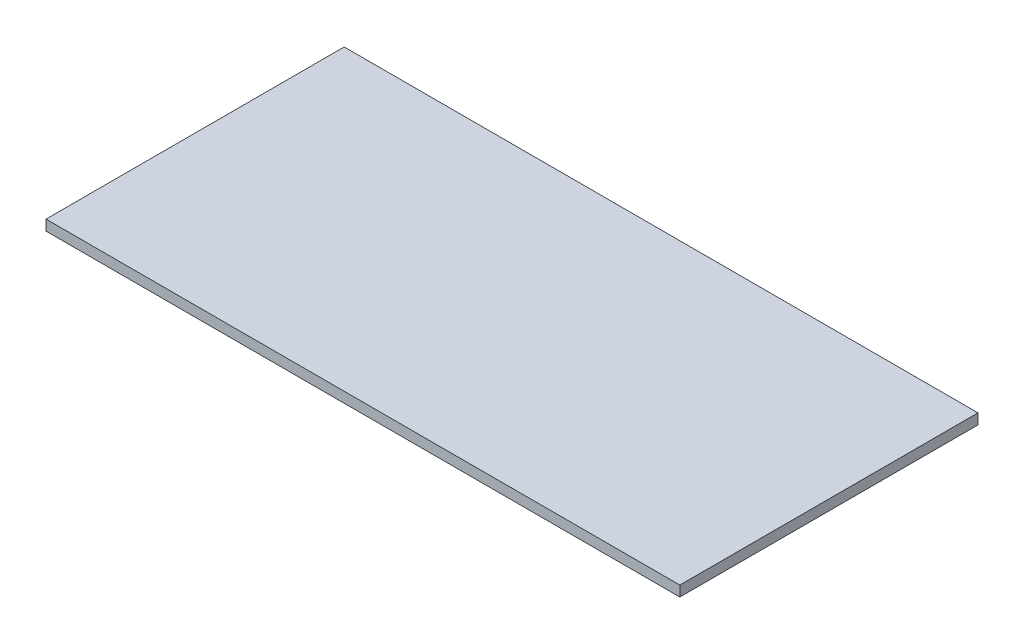
SolidWorks part; units mm, degrees
ref_plane "Front Plane" through (0, 0, 0) normal (0, 0, 1) x (1, 0, 0)
ref_plane "Top Plane" through (0, 0, 0) normal (0, 1, 0) x (1, 0, 0)
ref_plane "Right Plane" through (0, 0, 0) normal (1, 0, 0) x (0, 0, -1)
sketch "Sketch1" plane through (0, 0, 0) normal (0, 1, 0) x (1, 0, 0)
  line L1 (-457, -215) -> (457, -215)
  line L2 (-457, -215) -> (-457, 215)
  line L3 (-457, 215) -> (457, 215)
  line L4 (457, -215) -> (457, 215)
  line L5 (-457, -215) -> (457, 215) construction
  line L6 (-457, 215) -> (457, -215) construction
  point P0 (0, 0)
  dimension "D1" = 914
  dimension "D2" = 430
extrude "Boss-Extrude1" add sketch "Sketch1" along normal blind 15
sketch "Sketch2" plane through (0, 15, 0) normal (0, 1, 0) x (1, 0, 0)
  line L1 (364.7269, -182.6853) -> (381.3018, -182.6853)
  line L2 (357.7269, -175.6853) -> (357.7269, 175.6853)
  line L3 (364.7269, 182.6853) -> (381.3018, 182.6853)
  line L4 (388.3018, -175.6853) -> (388.3018, 175.6853)
  line L5 (357.7269, -182.6853) -> (388.3018, 182.6853) construction
  line L6 (357.7269, 182.6853) -> (388.3018, -182.6853) construction
  arc A0 (364.7269, -182.6853) -> (357.7269, -175.6853) centre (364.7269, -175.6853) cw
  arc A1 (381.3018, -182.6853) -> (388.3018, -175.6853) centre (381.3018, -175.6853) ccw
  arc A2 (381.3018, 182.6853) -> (388.3018, 175.6853) centre (381.3018, 175.6853) cw
  arc A3 (364.7269, 182.6853) -> (357.7269, 175.6853) centre (364.7269, 175.6853) ccw
  point P0 (373.0143, 0)
  dimension "D1" = 7
